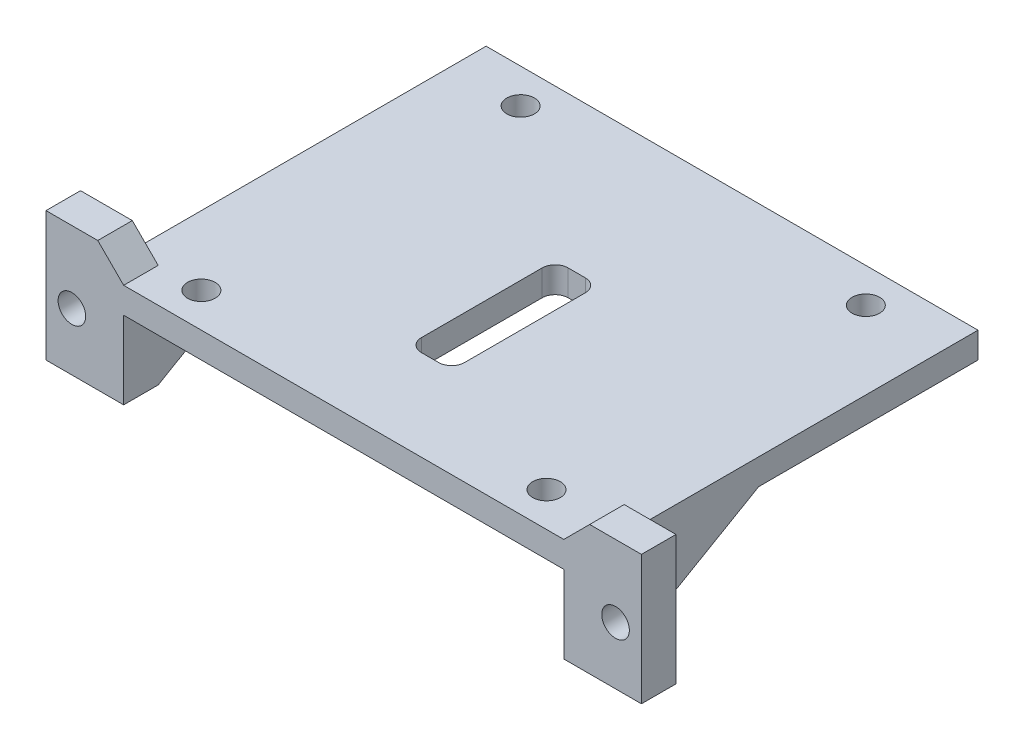
SolidWorks part; units mm, degrees
ref_plane "前视基准面" through (0, 0, 0) normal (0, 0, 1) x (1, 0, 0)
ref_plane "上视基准面" through (0, 0, 0) normal (0, 1, 0) x (1, 0, 0)
ref_plane "右视基准面" through (0, 0, 0) normal (1, 0, 0) x (0, 0, -1)
sketch "草图1" plane through (0, 0, 0) normal (0, 1, 0) x (1, 0, 0)
  line L1 (0, 0) -> (57, 0)
  line L2 (0, 0) -> (0, 45)
  line L3 (0, 45) -> (57, 45)
  line L4 (57, 0) -> (57, 45)
  dimension "D1" = 45
  dimension "D2" = 57
extrude "凸台-拉伸1" add sketch "草图1" along normal blind 3
sketch "草图2" plane through (0, 0, 0) normal (-1, 0, 0) x (0, 0, 1)
  line L0 (0, 6) -> (-4, 6)
  line L1 (-4, 6) -> (-4, -9)
  line L2 (-4, -9) -> (0, -9)
  line L3 (0, -9) -> (0, 6)
  line L4 (-45, 3) -> (0, 3) construction
  line L5 (-45, 0) -> (0, 0) construction
  line L8 (0, 3) -> (0, 0) construction
  dimension "D1" = 3
  dimension "D2" = 9
  dimension "D3" = 4
extrude "凸台-拉伸2" add sketch "草图2" along normal blind 6
sketch "草图3" plane through (57, 0, 0) normal (1, 0, 0) x (0, 0, -1)
  line L0 (0, 6) -> (0, -9)
  line L1 (0, -9) -> (4, -9)
  line L2 (4, -9) -> (4, 6)
  line L3 (4, 6) -> (0, 6)
extrude "凸台-拉伸3" add sketch "草图3" along normal blind 6
sketch "草图4" plane through (57, 0, 0) normal (-1, 0, 0) x (0, 0, 1)
  line L0 (-4, -9) -> (-19.5885, 0)
  line L1 (-4, 0) -> (-45, 0) construction
  line L2 (-19.5885, 0) -> (0, 0)
  line L3 (0, 0) -> (0, -9)
  line L4 (0, -9) -> (-4, -9)
  dimension "D1" = 30
extrude "凸台-拉伸4" add sketch "草图4" along normal blind 3
sketch "草图5" plane through (0, 0, 0) normal (1, 0, 0) x (0, 0, -1)
  line L0 (0, 0.3045) -> (0, -9)
  line L1 (0, -9) -> (4, -9)
  line L2 (4, -9) -> (19.5885, 0)
  line L3 (45, 0) -> (4, 0) construction
  line L4 (19.5885, 0) -> (0, 0)
  line M3 (4, -9) -> (4, 0)
  line M4 (4, 0) -> (0, 0)
  line M5 (0, 0) -> (0, -9)
  line M6 (0, -9) -> (4, -9)
  dimension "D1" = 30
extrude "凸台-拉伸5" add sketch "草图5" along normal blind 3 contours L2 L4 M3 | M6 M3 M4 M5 region at (0, -4.5, -2) region at (0, -3, -9.1962)
chamfer "倒角1" distance 3 angle 45 2 edges at (0, 3, -2) (57, 3, -2)
sketch "草图6" plane through (0, 0, -4) normal (0, 0, -1) x (-1, 0, 0)
  line L0 (-60, -2.3233) -> (3, -2.3233) construction
  line L1 (-63, -9) -> (-63, 6) construction
  line L2 (6, 6) -> (6, -9) construction
  circle A0 centre (3, -2.3233) radius 1.6
  circle A1 centre (-60, -2.3233) radius 1.6
  dimension "D1" = 3
  dimension "D2" = 3
extrude "切除-拉伸1" cut sketch "草图6" against normal blind 4
sketch "草图7" plane through (0, 3, 0) normal (0, 1, 0) x (1, 0, 0)
  line L0 (28, 49.7957) -> (28, -5.721) construction
  line L1 (8, 41) -> (8, 4)
  line L2 (3, 0) -> (54, 0) construction
  line L3 (0, 45) -> (0, 4) construction
  line L4 (48, 41) -> (48, 4)
  circle A0 centre (8, 41) radius 1.6
  circle A1 centre (8, 4) radius 1.6
  circle A2 centre (48, 4) radius 1.6
  circle A3 centre (48, 41) radius 1.6
  dimension "D1" = 37
  dimension "D2" = 4
  dimension "D3" = 8
extrude "切除-拉伸2" cut sketch "草图7" against normal blind 3 contours A3 | A2 | A0 | A1 region at (49.0994, 3, -5.0994) region at (46.9006, 3, -42.0994)
sketch "草图8" plane through (0, 0, 0) normal (0, -1, 0) x (1, 0, 0)
  line L0 (24, -45) -> (32, -45)
  line L1 (57, -45) -> (0, -45) construction
  line L2 (32, -45) -> (32, -42)
  line L3 (32, -42) -> (24, -42)
  line L4 (24, -42) -> (24, -45)
  line L5 (28, 5.34) -> (28, -50.6665) construction
  line L6 (0, -45) -> (0, -19.5885) construction
  point P10 (32, -43.5)
  dimension "D1" = 28
  dimension "D2" = 3
  dimension "D3" = 8
  dimension "D4" = 4
extrude "凸台-拉伸6" add sketch "草图8" along normal blind 9
sketch "草图9" plane through (32, 0, 0) normal (1, 0, 0) x (0, 0, -1)
  line L0 (45, 0) -> (29.1467, 0)
  line L1 (29.1467, 0) -> (42, -9)
  line L2 (42, -9) -> (45, -9)
  line L3 (45, -9) -> (45, 0)
  dimension "D1" = 35
extrude "凸台-拉伸7" add sketch "草图9" along normal blind 3
sketch "草图10" plane through (24, 0, 0) normal (-1, 0, 0) x (0, 0, 1)
  line L0 (-45, 0) -> (-45, -9)
  line L1 (-45, -9) -> (-42, -9)
  line L2 (-42, -9) -> (-29.1467, 0)
  line L3 (-29.1467, 0) -> (-45, 0)
extrude "凸台-拉伸8" add sketch "草图10" along normal blind 3
sketch "草图11" plane through (0, 0, -42) normal (0, 0, 1) x (1, 0, 0)
  line L0 (24, -9) -> (24, 0) construction
  line L1 (32, -9) -> (24, -9) construction
  circle A0 centre (28, -4.5) radius 1.6
  dimension "D1" = 4
  dimension "D2" = 4.5
extrude "切除-拉伸3" cut sketch "草图11" against normal blind 3
sketch "草图12" plane through (0, 3, 0) normal (0, 1, 0) x (1, 0, 0)
  line L0 (28, 49.4691) -> (28, -3.816) construction
  line L1 (25.5, 27.5) -> (25.5, 10.5)
  line L2 (25.5, 10.5) -> (30.5, 10.5)
  line L3 (30.5, 10.5) -> (30.5, 27.5)
  line L4 (30.5, 27.5) -> (25.5, 27.5)
  line L5 (0, 45) -> (0, 4) construction
  line L6 (-5.009, 22.5) -> (59.3487, 22.5) construction
  line L7 (3, 0) -> (54, 0) construction
  dimension "D1" = 28
  dimension "D2" = 2.5
  dimension "D3" = 2.5
  dimension "D4" = 22.5
  dimension "D5" = 5
  dimension "D6" = 12
extrude "切除-拉伸4" cut sketch "草图12" against normal blind 3
fillet "圆角1" radius 1.5 4 edges at (30.5, 1.5, -10.5) (25.5, 1.5, -10.5) (25.5, 1.5, -27.5) (30.5, 1.5, -27.5)
